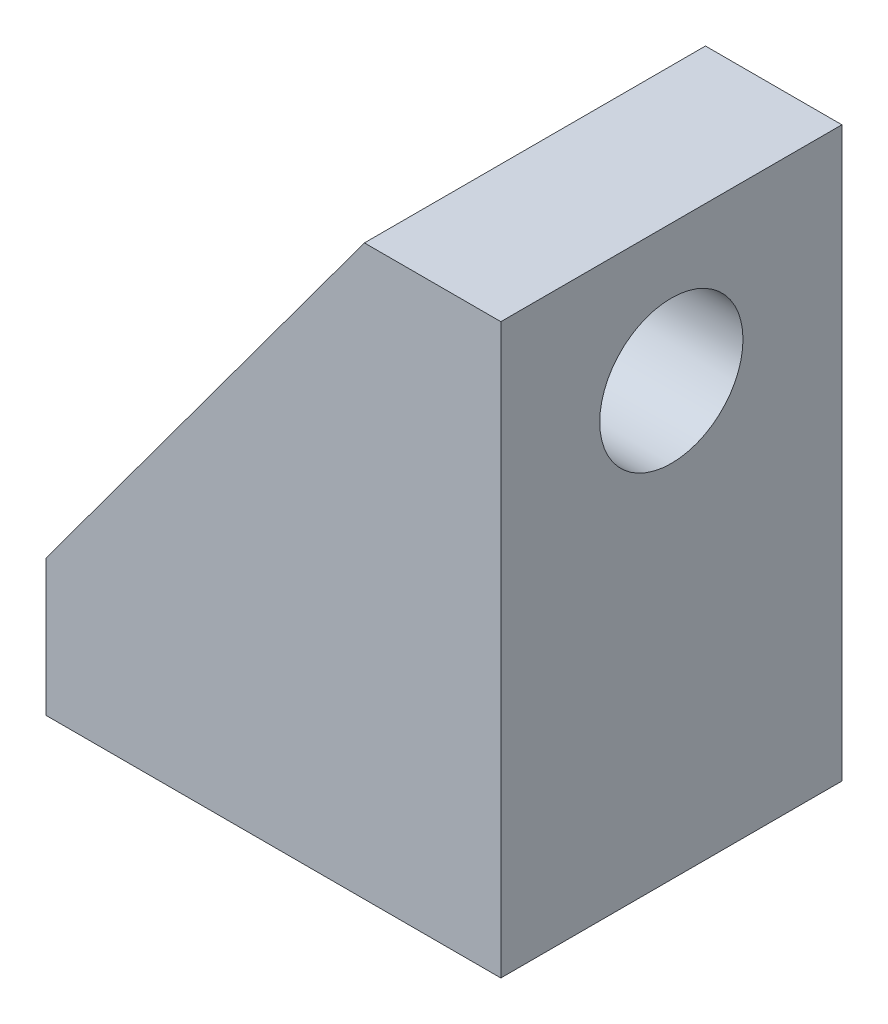
SolidWorks part; units mm, degrees
ref_plane "Front Plane" through (0, 0, 0) normal (0, 0, 1) x (1, 0, 0)
ref_plane "Top Plane" through (0, 0, 0) normal (0, 1, 0) x (1, 0, 0)
ref_plane "Right Plane" through (0, 0, 0) normal (1, 0, 0) x (0, 0, -1)
sketch "Sketch3" plane through (0, 0, 0) normal (0, 0, 1) x (1, 0, 0)
  line L0 (18.3468, 0) -> (38.3468, 0)
  line L1 (8.25, 0) -> (-8.25, 0) construction
  line L2 (38.3468, 0) -> (38.3468, 25)
  line L4 (18.3468, 0) -> (18.3468, 6)
  line L6 (38.3468, 25) -> (32.3468, 25)
  line L8 (18.3468, 6) -> (32.3468, 25)
  dimension "D1" = 20
  dimension "D2" = 25
  dimension "D3" = 6
  dimension "D4" = 6
extrude "Boss-Extrude2" add sketch "Sketch3" along normal blind 15 contours L4 | L2 L0 region at (30.2796, 10.2652, 0)
ref_plane "Plane1" through (0, 20, 0) normal (0, 1, 0) x (1, 0, 0)
sketch "Sketch4" plane through (0, 20, 0) normal (0, 1, 0) x (1, 0, 0)
  line L1 (38.3468, -15) -> (38.3468, 0) construction
  line L2 (-11, 0) -> (11, 0) construction
  circle A0 centre (25.2704, -7.5) radius 3.15
  circle A1 centre (25.2704, -7.5) radius 5.5
  dimension "D1" = 6.3
  dimension "D2" = 11
  dimension "D3" = 13.0764
  dimension "D4" = 7.5
extrude "Cut-Extrude1" cut sketch "Sketch4" against normal through all contours A0 region at (25.2704, 20, 7.5)
extrude "Cut-Extrude2" cut sketch "Sketch4<3>" against normal blind 14
sketch "Sketch4<3>" plane through (0, 20, 0) normal (0, 1, 0) x (1, 0, 0) same geometry as "Sketch4"
sketch "Sketch6" plane through (0, 0, 0) normal (1, 0, 0) x (0, 0, -1)
  line L1 (8.25, 0) -> (-8.25, 0) construction
  line L2 (-15, 0) -> (-15, 25) construction
  circle A0 centre (-7.5, 19) radius 3.15
  circle A1 centre (-7.5, 19) radius 5.5
  dimension "D1" = 6.3
  dimension "D2" = 11
  dimension "D3" = 19
  dimension "D4" = 7.5
extrude "Cut-Extrude3" cut sketch "Sketch6" along normal through all contours A0 region at (0, 19, 7.5)
extrude "Cut-Extrude4" cut sketch "Sketch6<3>" along normal offset from surface (32.3468 mm away) 6 up to face at (38.3468, 19, 4.35)
sketch "Sketch6<3>" plane through (0, 0, 0) normal (1, 0, 0) x (0, 0, -1) same geometry as "Sketch6"
